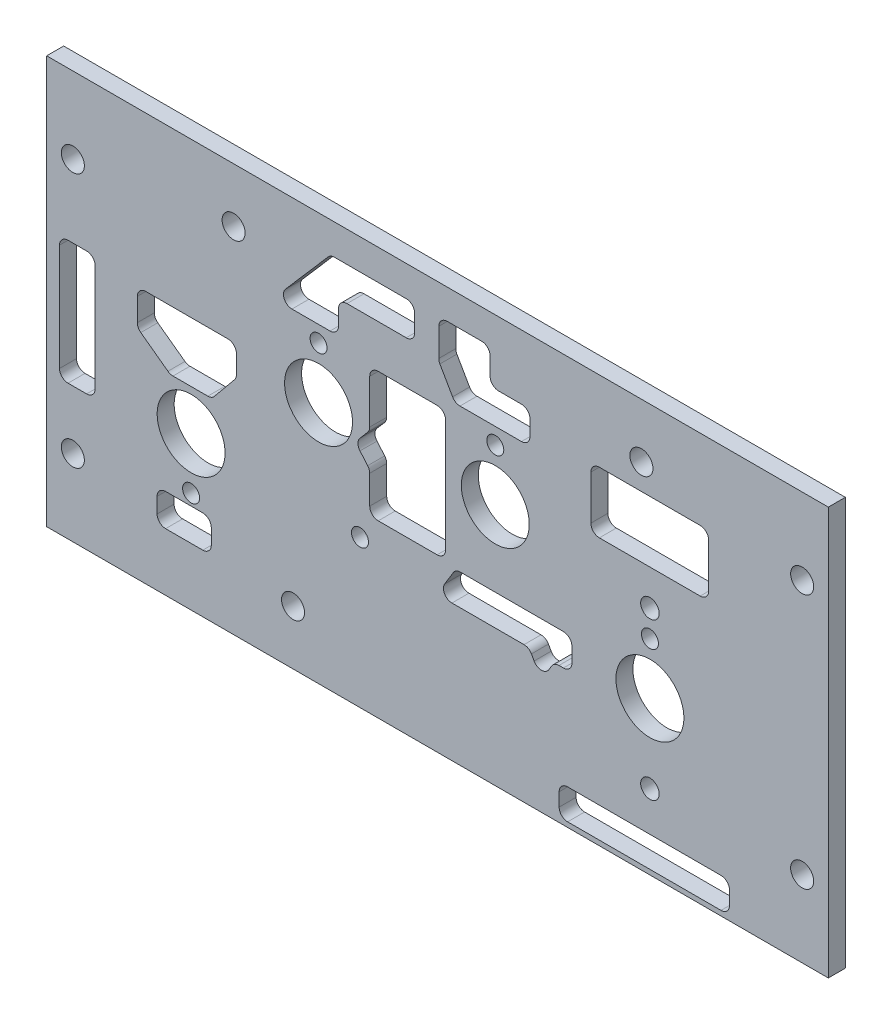
SolidWorks part; units mm, degrees
ref_plane "Front Plane" through (0, 0, 0) normal (0, 0, 1) x (1, 0, 0)
ref_plane "Top Plane" through (0, 0, 0) normal (0, 1, 0) x (1, 0, 0)
ref_plane "Right Plane" through (0, 0, 0) normal (1, 0, 0) x (0, 0, -1)
sketch "Sketch1" plane through (0, 0, 0) normal (0, 0, 1) x (1, 0, 0)
  line L4 (0, 76.2) -> (-146.05, 76.2)
  line L5 (-146.05, 76.2) -> (-146.05, 0)
  line L6 (-146.05, 0) -> (0, 0)
  line L7 (0, 0) -> (0, 76.2)
  line L8 (0, 76.2) -> (-146.05, 76.2)
  line L9 (-146.05, 76.2) -> (-146.05, 0)
  line L10 (-146.05, 0) -> (0, 0)
  line L11 (0, 0) -> (0, 76.2)
  dimension "D1" = 0
extrude "Boss-Extrude1" add sketch "Sketch1" against normal blind 3.175
hole_wizard "1/8 (0.125) Diameter Hole1" positions "Sketch3" profile "Sketch2" hole size "1/8" standard "ANSI Inch" end condition through all
sketch "Sketch3" plane through (0, 0, -3.175) normal (0, 0, -1) x (-1, 0, 0)
  circle A0 centre (95.25, 45.466) radius 9.652 construction
  circle A1 centre (119.0625, 28.575) radius 9.652 construction
  circle A2 centre (62.23, 45.466) radius 9.652 construction
  circle A3 centre (33.3375, 28.575) radius 9.652 construction
  point P0 (95.25, 55.118)
  point P4 (119.0625, 18.923)
  point P8 (62.23, 55.118)
  point P12 (33.3375, 38.227)
sketch "Sketch2" plane through (-95.25, 55.118, -3.175) normal (1, 0, 0) x (0, 1, 0)
  line L0 (0, 0) -> (0, 3.175)
  line L1 (0, 3.175) -> (1.5875, 3.175)
  line L2 (1.5875, 3.175) -> (1.5875, 0)
  line L5 (1.5875, 0) -> (0, 0)
  line L11 (0, -6.35) -> (0, 107.95) construction
  dimension "Thru Hole Dia." = 3.175
  dimension "Thru Hole Depth" = 3.175
hole_wizard "1/2 (0.5) Diameter Hole1" positions "Sketch5" profile "Sketch4" hole size "1/2" standard "ANSI Inch" end condition through all
sketch "Sketch5" plane through (0, 0, -3.175) normal (0, 0, -1) x (-1, 0, 0)
  point P0 (95.25, 45.466)
  point P3 (119.0625, 28.575)
  point P6 (62.23, 45.466)
  point P9 (33.3375, 28.575)
sketch "Sketch4" plane through (-95.25, 45.466, -3.175) normal (1, 0, 0) x (0, 1, 0)
  line L0 (0, 0) -> (0, 3.175)
  line L1 (0, 3.175) -> (6.35, 3.175)
  line L2 (6.35, 3.175) -> (6.35, 0)
  line L5 (6.35, 0) -> (0, 0)
  line L11 (0, -6.35) -> (0, 107.95) construction
  dimension "Thru Hole Dia." = 12.7
  dimension "Thru Hole Depth" = 3.175
hole_wizard "#6 Clearance Hole1" positions "Sketch7" profile "Sketch6" hole size "#6" standard "ANSI Inch" end condition through all
sketch "Sketch7" plane through (0, 0, -3.175) normal (0, 0, -1) x (-1, 0, 0)
  point P0 (141.1605, 61.9125)
  point P3 (141.1605, 14.2875)
  point P6 (4.8895, 61.9125)
  point P10 (4.8895, 14.2875)
  point P13 (111.125, 66.04)
  point P16 (100.015, 10.16)
  point P19 (34.925, 66.04)
sketch "Sketch6" plane through (-141.1605, 61.9125, -3.175) normal (1, 0, 0) x (0, 1, 0)
  line L0 (0, 0) -> (0, 3.175)
  line L1 (0, 3.175) -> (2.1526, 3.175)
  line L2 (2.1526, 3.175) -> (2.1526, 0)
  line L5 (2.1526, 0) -> (0, 0)
  line L11 (0, -6.35) -> (0, 107.95) construction
  dimension "Thru Hole Dia." = 4.3053
  dimension "Thru Hole Depth" = 3.175
hole_wizard "#4 Clearance Hole1" positions "Sketch9" profile "Sketch8" hole size "#4" standard "ANSI Inch" end condition through all
sketch "Sketch9" plane through (0, 0, -3.175) normal (0, 0, -1) x (-1, 0, 0)
  point P0 (33.3375, 43.18)
  point P3 (33.3375, 13.97)
sketch "Sketch8" plane through (-33.3375, 43.18, -3.175) normal (1, 0, 0) x (0, 1, 0)
  line L0 (0, 0) -> (0, 3.175)
  line L1 (0, 3.175) -> (1.7272, 3.175)
  line L2 (1.7272, 3.175) -> (1.7272, 0)
  line L5 (1.7272, 0) -> (0, 0)
  line L11 (0, -6.35) -> (0, 107.95) construction
  dimension "Thru Hole Dia." = 3.4544
  dimension "Thru Hole Depth" = 3.175
sketch "Sketch11" plane through (0, 0, -3.175) normal (0, 0, -1) x (-1, 0, 0)
  line L0 (23.9487, 61.26) -> (42.7833, 61.26)
  line L1 (44.3708, 59.6725) -> (44.3708, 51.4195)
  line L2 (22.3612, 59.6725) -> (22.3612, 51.4195)
  line L3 (23.9487, 49.832) -> (42.7833, 49.832)
  line L4 (64.7801, 70.6544) -> (71.2013, 70.6544)
  line L5 (72.7888, 69.0669) -> (72.7888, 63.8628)
  line L6 (72.5784, 63.0729) -> (70.2067, 58.9385)
  line L7 (68.8296, 58.1409) -> (57.3334, 58.1409)
  line L8 (55.7459, 59.7284) -> (55.7459, 62.5959)
  line L9 (63.1926, 69.0669) -> (63.1926, 65.7709)
  line L10 (61.6051, 64.1834) -> (57.3334, 64.1834)
  line L11 (78.8708, 70.4894) -> (92.27, 70.4894)
  line L12 (93.4697, 69.9417) -> (101.4203, 60.7681)
  line L13 (100.2206, 58.1409) -> (93.1099, 58.1409)
  line L14 (91.5224, 59.7284) -> (91.5224, 62.5791)
  line L15 (89.9349, 64.1666) -> (78.8708, 64.1666)
  line L16 (77.2833, 65.7541) -> (77.2833, 68.9019)
  line L17 (73.0966, 56.1163) -> (84.102, 56.1163)
  line L18 (85.6895, 54.5288) -> (85.6895, 46.3055)
  line L19 (86.0744, 45.2692) -> (87.505, 43.609)
  line L20 (87.5071, 41.5388) -> (86.0723, 39.8671)
  line L21 (85.6895, 38.8332) -> (85.6895, 33.5149)
  line L22 (84.102, 31.9274) -> (73.0966, 31.9274)
  line L23 (71.5091, 33.5149) -> (71.5091, 54.5288)
  line L24 (49.4951, 31.3075) -> (68.7282, 31.3075)
  line L25 (70.0828, 30.5478) -> (71.681, 27.9323)
  line L26 (70.3264, 25.517) -> (56.8566, 25.517)
  line L27 (55.4728, 24.7074) -> (54.969, 23.8112)
  line L28 (52.2305, 23.7613) -> (51.6843, 24.6551)
  line L29 (50.3297, 25.4149) -> (49.4951, 25.4149)
  line L30 (47.9076, 27.0024) -> (47.9076, 29.72)
  line L31 (138.5892, 48.3487) -> (142.062, 48.3487)
  line L32 (143.6495, 46.7612) -> (143.6495, 26.8106)
  line L33 (142.062, 25.2231) -> (138.5892, 25.2231)
  line L34 (137.0017, 26.8106) -> (137.0017, 46.7612)
  line L35 (112.188, 47.3287) -> (127.5281, 47.3287)
  line L36 (129.1156, 45.7412) -> (129.1156, 41.4887)
  line L37 (128.4662, 40.2081) -> (123.3903, 36.4895)
  line L38 (122.4521, 36.1826) -> (115.9411, 36.1826)
  line L39 (114.714, 36.7629) -> (110.9609, 41.3351)
  line L40 (110.6005, 42.3423) -> (110.6005, 45.7412)
  line L41 (20.051, 6.572) -> (48.7123, 6.572)
  line L42 (50.2998, 4.9845) -> (50.2998, 2.5039)
  line L43 (48.7123, 0.9164) -> (20.051, 0.9164)
  line L44 (18.4635, 2.5039) -> (18.4635, 4.9845)
  line L45 (116.8817, 16.8216) -> (123.8316, 16.8216)
  line L46 (125.4191, 15.2341) -> (125.4191, 12.383)
  line L47 (123.8316, 10.7955) -> (116.8817, 10.7955)
  line L48 (115.2942, 12.383) -> (115.2942, 15.2341)
  arc A0 (63.1926, 65.7709) -> (61.6051, 64.1834) centre (61.6051, 65.7709) cw
  arc A1 (64.7801, 70.6544) -> (63.1926, 69.0669) centre (64.7801, 69.0669) ccw
  arc A2 (71.2013, 70.6544) -> (72.7888, 69.0669) centre (71.2013, 69.0669) cw
  arc A3 (72.7888, 63.8628) -> (72.5784, 63.0729) centre (71.2013, 63.8628) cw
  arc A4 (70.2067, 58.9385) -> (68.8296, 58.1409) centre (68.8296, 59.7284) cw
  arc A5 (57.3334, 58.1409) -> (55.7459, 59.7284) centre (57.3334, 59.7284) cw
  arc A6 (55.7459, 62.5959) -> (57.3334, 64.1834) centre (57.3334, 62.5959) cw
  arc A7 (101.4203, 60.7681) -> (100.2206, 58.1409) centre (100.2206, 59.7284) cw
  arc A8 (93.1099, 58.1409) -> (91.5224, 59.7284) centre (93.1099, 59.7284) cw
  arc A9 (91.5224, 62.5791) -> (89.9349, 64.1666) centre (89.9349, 62.5791) ccw
  arc A10 (92.27, 70.4894) -> (93.4697, 69.9417) centre (92.27, 68.9019) cw
  arc A11 (78.8708, 70.4894) -> (77.2833, 68.9019) centre (78.8708, 68.9019) ccw
  arc A12 (78.8708, 64.1666) -> (77.2833, 65.7541) centre (78.8708, 65.7541) cw
  arc A13 (73.0966, 31.9274) -> (71.5091, 33.5149) centre (73.0966, 33.5149) cw
  arc A14 (85.6895, 33.5149) -> (84.102, 31.9274) centre (84.102, 33.5149) cw
  arc A15 (86.0723, 39.8671) -> (85.6895, 38.8332) centre (87.277, 38.8332) ccw
  arc A16 (85.6895, 46.3055) -> (86.0744, 45.2692) centre (87.277, 46.3055) ccw
  arc A17 (87.505, 43.609) -> (87.5071, 41.5388) centre (86.3024, 42.5727) cw
  arc A18 (84.102, 56.1163) -> (85.6895, 54.5288) centre (84.102, 54.5288) cw
  arc A19 (73.0966, 56.1163) -> (71.5091, 54.5288) centre (73.0966, 54.5288) ccw
  arc A20 (49.4951, 25.4149) -> (47.9076, 27.0024) centre (49.4951, 27.0024) cw
  arc A21 (51.6843, 24.6551) -> (50.3297, 25.4149) centre (50.3297, 23.8274) ccw
  arc A22 (54.969, 23.8112) -> (52.2305, 23.7613) centre (53.5851, 24.589) cw
  arc A23 (56.8566, 25.517) -> (55.4728, 24.7074) centre (56.8566, 23.9295) ccw
  arc A24 (71.681, 27.9323) -> (70.3264, 25.517) centre (70.3264, 27.1045) cw
  arc A25 (68.7282, 31.3075) -> (70.0828, 30.5478) centre (68.7282, 29.72) cw
  arc A26 (49.4951, 31.3075) -> (47.9076, 29.72) centre (49.4951, 29.72) ccw
  circle A27 centre (87.5071, 27.5651) radius 1.5875
  arc A28 (138.5892, 25.2231) -> (137.0017, 26.8106) centre (138.5892, 26.8106) cw
  arc A29 (143.6495, 26.8106) -> (142.062, 25.2231) centre (142.062, 26.8106) cw
  arc A30 (142.062, 48.3487) -> (143.6495, 46.7612) centre (142.062, 46.7612) cw
  arc A31 (138.5892, 48.3487) -> (137.0017, 46.7612) centre (138.5892, 46.7612) ccw
  arc A32 (110.9609, 41.3351) -> (110.6005, 42.3423) centre (112.188, 42.3423) cw
  arc A33 (115.9411, 36.1826) -> (114.714, 36.7629) centre (115.9411, 37.7701) cw
  arc A34 (123.3903, 36.4895) -> (122.4521, 36.1826) centre (122.4521, 37.7701) cw
  arc A35 (129.1156, 41.4887) -> (128.4662, 40.2081) centre (127.5281, 41.4887) cw
  arc A36 (127.5281, 47.3287) -> (129.1156, 45.7412) centre (127.5281, 45.7412) cw
  arc A37 (112.188, 47.3287) -> (110.6005, 45.7412) centre (112.188, 45.7412) ccw
  arc A38 (20.051, 0.9164) -> (18.4635, 2.5039) centre (20.051, 2.5039) cw
  arc A39 (50.2998, 2.5039) -> (48.7123, 0.9164) centre (48.7123, 2.5039) cw
  arc A40 (48.7123, 6.572) -> (50.2998, 4.9845) centre (48.7123, 4.9845) cw
  arc A41 (20.051, 6.572) -> (18.4635, 4.9845) centre (20.051, 4.9845) ccw
  arc A42 (123.8316, 16.8216) -> (125.4191, 15.2341) centre (123.8316, 15.2341) cw
  arc A43 (125.4191, 12.383) -> (123.8316, 10.7955) centre (123.8316, 12.383) cw
  arc A44 (116.8817, 10.7955) -> (115.2942, 12.383) centre (116.8817, 12.383) cw
  arc A45 (116.8817, 16.8216) -> (115.2942, 15.2341) centre (116.8817, 15.2341) ccw
  arc A46 (42.7833, 61.26) -> (44.3708, 59.6725) centre (42.7833, 59.6725) cw
  arc A47 (44.3708, 51.4195) -> (42.7833, 49.832) centre (42.7833, 51.4195) cw
  arc A48 (22.3612, 51.4195) -> (23.9487, 49.832) centre (23.9487, 51.4195) ccw
  arc A49 (23.9487, 61.26) -> (22.3612, 59.6725) centre (23.9487, 59.6725) ccw
  dimension "D1" = 1.5875
  dimension "D2" = 1.5875
  dimension "D3" = 1.5875
  dimension "D4" = 1.5875
  dimension "D5" = 3.175
  dimension "D6" = 1.5875
  dimension "D7" = 1.5875
  dimension "D8" = 1.5875
  dimension "D9" = 1.5875
  dimension "D10" = 1.5875
extrude "Cut-Extrude1" cut sketch "Sketch11" against normal through all
